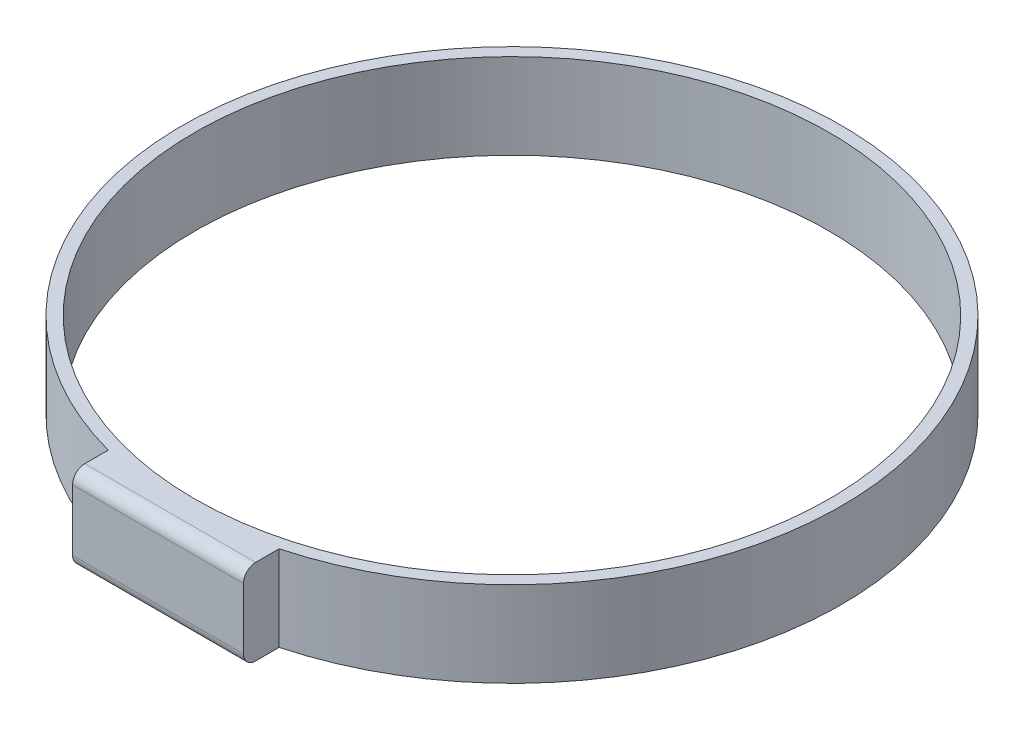
SolidWorks part; units mm, degrees
material "AISI 316 Stainless Steel Sheet (SS)"
ref_plane "Front Plane" through (0, 0, 0) normal (0, 0, 1) x (1, 0, 0)
ref_plane "Top Plane" through (0, 0, 0) normal (0, 1, 0) x (1, 0, 0)
ref_plane "Right Plane" through (0, 0, 0) normal (1, 0, 0) x (0, 0, -1)
sketch "Sketch1" plane through (0, 0, 0) normal (0, 1, 0) x (1, 0, 0)
  circle A0 centre (0, 0) radius 26
  circle A1 centre (0, 0) radius 27
  dimension "D1" = 52
  dimension "D2" = 1
extrude "Boss-Extrude1" add sketch "Sketch1" along normal blind 7
ref_plane "Plane1" through (0, 0, 26) normal (0, 0, 1) x (1, 0, 0)
sketch "Sketch2" plane through (0, 0, 26) normal (0, 0, 1) x (1, 0, 0)
  line L0 (26, 7) -> (-26, 7) construction
  line L1 (-7, 7) -> (7, 7)
  line L2 (-7, 7) -> (-7, 0)
  line L3 (-7, 0) -> (7, 0)
  line L4 (7, 7) -> (7, 0)
  line L5 (-27, 0) -> (27, 0) construction
  dimension "D1" = 14
extrude "Boss-Extrude2" add sketch "Sketch2" along normal blind 3
fillet "Fillet1" radius 1 2 edges at (0, 0, 29) (0, 7, 29)
